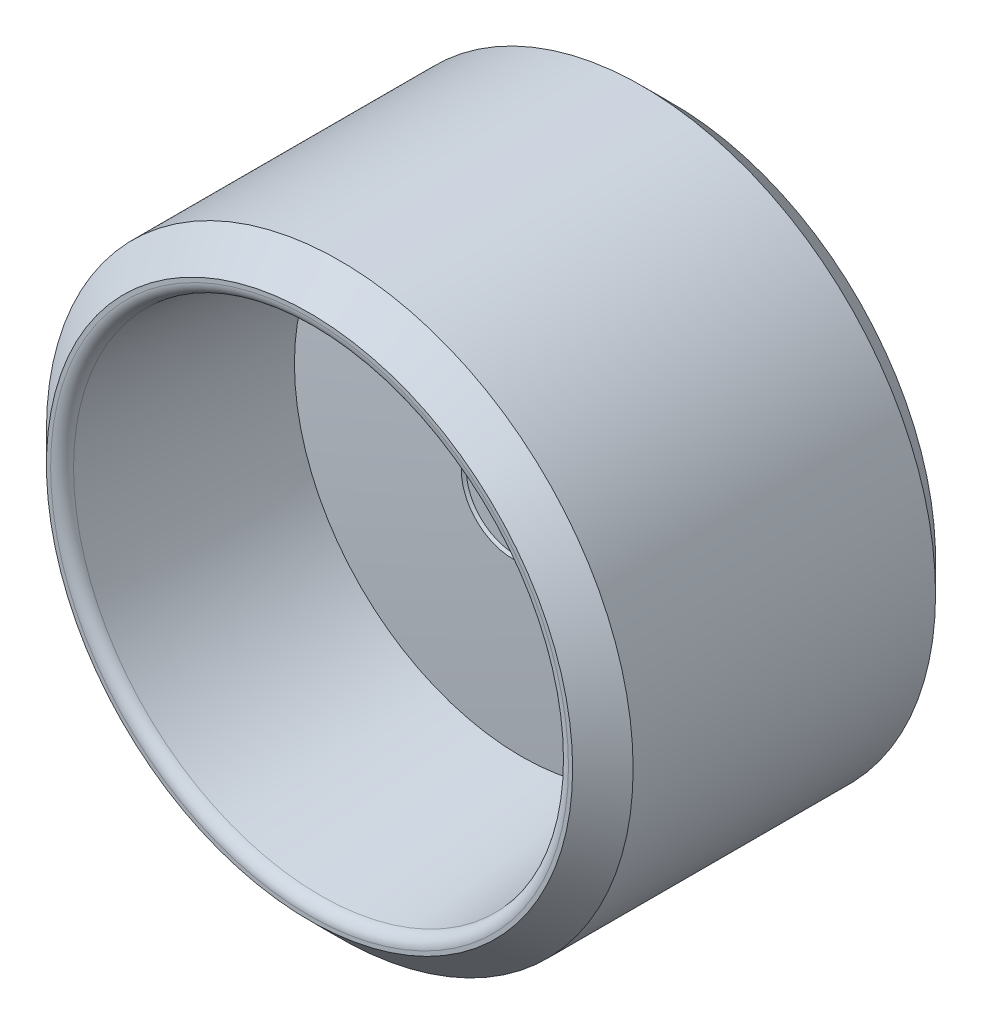
SolidWorks part; units mm, degrees
ref_plane "정면" through (0, 0, 0) normal (0, 0, 1) x (1, 0, 0)
ref_plane "윗면" through (0, 0, 0) normal (0, 1, 0) x (1, 0, 0)
ref_plane "우측면" through (0, 0, 0) normal (1, 0, 0) x (0, 0, -1)
sketch "스케치1" plane through (0, 0, 0) normal (0, 1, 0) x (1, 0, 0)
  line L0 (0, 0) -> (4, 0)
  line L1 (4, 0) -> (5.8947, 2)
  line L2 (5.8947, 2) -> (9.7, 2)
  line L3 (9.7, 2) -> (9.7, -10)
  line L4 (9.7, -10) -> (8.2, -10)
  line L5 (8.2, -10) -> (7.5, -3)
  line L6 (7.5, -3) -> (0, -3) construction
  line L7 (0, -3) -> (0, 0)
  line L8 (0, -3.3) -> (0, -3)
  arc A0 (7.5, -3) -> (0, -3.3) centre (-0.2247, 96.2179) cw
  dimension "D1" = 9.7
  dimension "D2" = 3
  dimension "D3" = 12
  dimension "D4" = 4
  dimension "D5" = 7.5
  dimension "D6" = 2
  dimension "D7" = 0.3
  dimension "D8" = 1.5
revolve "회전1" add sketch "스케치1" angle 360 about L7
chamfer "모따기1" distance 1 angle 45 2 edges at (9.7, 0, -2) (9.7, 0, 10)
fillet "필렛1" radius 0.4 2 edges at (5.8947, 0, -2) (8.2, 0, 10)
ref_plane "평면1" through (0, 0, 10) normal (0, 0, 1) x (1, 0, 0)
sketch "스케치2" plane through (0, 0, 10) normal (0, 0, 1) x (1, 0, 0)
  circle A0 centre (0, 0) radius 1.5
  dimension "D1" = 3
extrude "컷-돌출1" cut sketch "스케치2" against normal blind 6.8
chamfer "모따기2" distance 0.2 angle 45 1 edges at (-1.5, 0, 3.2853)
